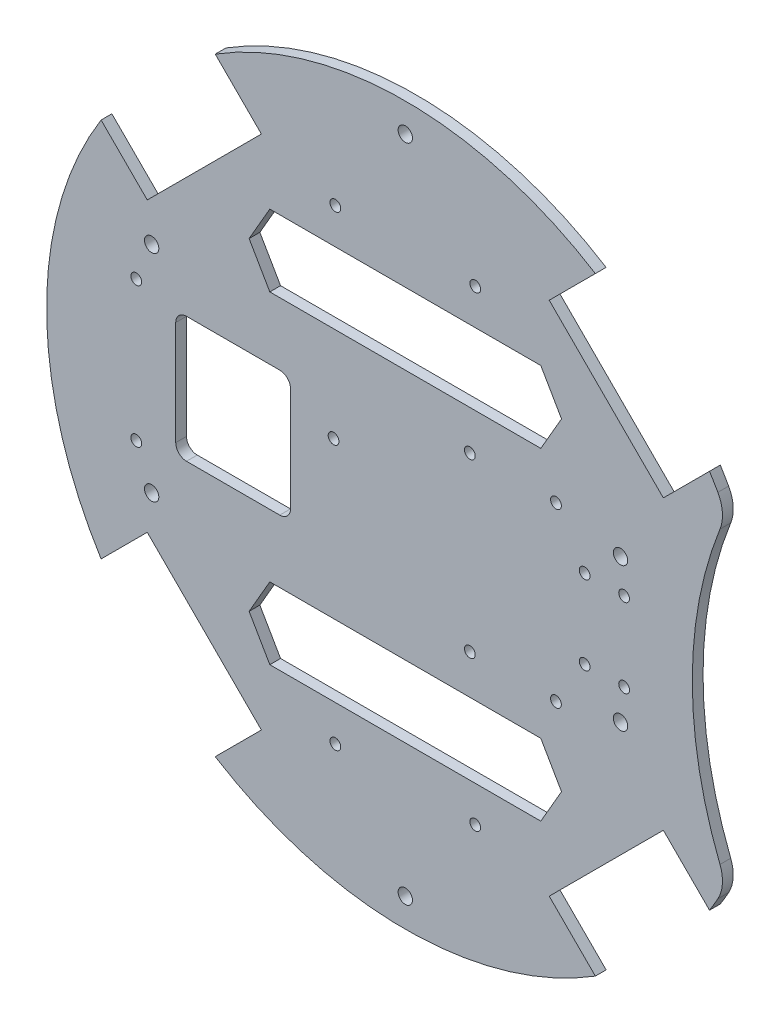
SolidWorks part; units mm, degrees
ref_plane "Alzado" through (0, 0, 0) normal (0, 0, 1) x (1, 0, 0)
ref_plane "Planta" through (0, 0, 0) normal (0, 1, 0) x (1, 0, 0)
ref_plane "Vista lateral" through (0, 0, 0) normal (1, 0, 0) x (0, 0, -1)
sketch "Croquis1" plane through (0, 0, 0) normal (0, 0, 1) x (1, 0, 0)
  circle A0 centre (0, 0) radius 100
  dimension "D1" = 200
extrude "Saliente-Extruir1" add sketch "Croquis1" along normal blind 3
sketch "Croquis3" plane through (0, 0, 3) normal (0, 0, 1) x (1, 0, 0)
  line L0 (0, 0) -> (190, 0) construction
  circle A0 centre (190, 0) radius 110
  dimension "D1" = 220
  dimension "D2" = 190
extrude "Cortar-Extruir1" cut sketch "Croquis3" against normal blind 3
fillet "Redondeo1" radius 10 2 edges at (89.4737, -44.6594, 1.5) (89.4737, 44.6594, 1.5)
sketch "Croquis7" plane through (0, 0, 3) normal (0, 0, 1) x (1, 0, 0)
  line L0 (-71.9393, -40.1195) -> (-40.1195, -71.9393)
  line L1 (-71.9393, -40.1195) -> (-89.617, -57.7972)
  line L2 (-40.1195, -71.9393) -> (-57.7972, -89.617)
  line L3 (-89.617, -57.7972) -> (-57.7972, -89.617)
  line L6 (0, -100) -> (0, 100) construction
  line L7 (-100, 0) -> (80, 0) construction
  line L8 (-40.1195, 71.9393) -> (-71.9393, 40.1195)
  line L9 (-40.1195, 71.9393) -> (-57.7972, 89.617)
  line L10 (-57.7972, 89.617) -> (-89.617, 57.7972)
  line L11 (-71.9393, 40.1195) -> (-89.617, 57.7972)
  line L12 (71.9393, 40.1195) -> (40.1195, 71.9393)
  line L13 (71.9393, 40.1195) -> (89.617, 57.7972)
  line L14 (89.617, 57.7972) -> (57.7972, 89.617)
  line L15 (40.1195, 71.9393) -> (57.7972, 89.617)
  line L16 (40.1195, -71.9393) -> (71.9393, -40.1195)
  line L17 (40.1195, -71.9393) -> (57.7972, -89.617)
  line L18 (57.7972, -89.617) -> (89.617, -57.7972)
  line L19 (71.9393, -40.1195) -> (89.617, -57.7972)
  line L20 (70.7107, -70.7107) -> (-70.7107, 70.7107) construction
  line L21 (-70.7107, -70.7107) -> (70.7107, 70.7107) construction
  arc A0 (87.1345, 49.0671) -> (87.1345, -49.0671) centre (0, 0) ccw construction
  arc A1 (87.1345, 49.0671) -> (87.1345, -49.0671) centre (0, 0) ccw construction
  arc A4 (87.7193, 40.4803) -> (87.7193, -40.4803) centre (190, 0) ccw construction
  point P24 (0, 0)
  dimension "D1" = 22.5
  dimension "D2" = 45
  dimension "D3" = 25
  dimension "D4" = 45
  dimension "D5" = 200
  dimension "D6" = 4
  dimension "D7" = 79.2376
  dimension "D8" = 22.5
  dimension "D9" = 200
  dimension "D10" = 45
  dimension "D11" = 90
  dimension "D12" = 79.2376
extrude "Cortar-Extruir3" cut sketch "Croquis7" against normal blind 10
sketch "Croquis10" plane through (0, 0, 3) normal (0, 0, 1) x (1, 0, 0)
  line L0 (80, 0) -> (-100, 0) construction
  circle A0 centre (-20, 8.5) radius 1.5
  arc A1 (-84.8075, 52.9877) -> (-84.8075, -52.9877) centre (0, 0) ccw construction
  arc A5 (87.7193, 40.4803) -> (87.7193, -40.4803) centre (190, 0) ccw construction
  point P5 (0, 0)
  dimension "D1" = 3
  dimension "D2" = 8.5
  dimension "D3" = 20
extrude "Cortar-Extruir4" cut sketch "Croquis10" against normal through all
sketch "Croquis12" plane through (0, 0, 0) normal (0, 0, -1) x (-1, 0, 0)
  line L0 (-80, 0) -> (100, 0) construction
  line L1 (-61, 0) -> (-61, -11) construction
  line L2 (-61, 0) -> (-61, 11) construction
  line L5 (-50, 11) -> (-50, -11) construction
  line L6 (0, 100) -> (0, -100) construction
  circle A4 centre (-61, 11) radius 1.5
  circle A6 centre (-61, -11) radius 1.5
  circle A7 centre (-50, 11) radius 1.5
  circle A8 centre (-50, -11) radius 1.5
  arc A9 (52.9877, 84.8075) -> (-52.9877, 84.8075) centre (0, 0) ccw construction
  arc A10 (-52.9877, -84.8075) -> (52.9877, -84.8075) centre (0, 0) ccw construction
  arc A11 (-87.7193, -40.4803) -> (-87.7193, 40.4803) centre (-190, 0) ccw construction
  arc A12 (84.8075, -52.9877) -> (84.8075, 52.9877) centre (0, 0) ccw construction
  dimension "D4" = 11
  dimension "D5" = 3
  dimension "D6" = 3
  dimension "D7" = 11
  dimension "D1" = 3
  dimension "D2" = 3
  dimension "D3" = 50
  dimension "D8" = 11
  dimension "D9" = 22
  dimension "D10" = 11
extrude "Cortar-Extruir6" cut sketch "Croquis12" against normal through all
sketch "Croquis13" plane through (0, 0, 0) normal (0, 0, -1) x (-1, 0, 0)
  line L0 (0, 100) -> (0, -100) construction
  line L1 (100, 0) -> (-100, 0) construction
  line L2 (-70.7107, -70.7107) -> (70.7107, 70.7107) construction
  line L3 (-70.7093, 70.7093) -> (70.712, -70.712) construction
  line L4 (-70.7093, 70.7093) -> (-70.7107, -70.7107) construction
  line L5 (-70.7107, -70.7107) -> (70.712, -70.712) construction
  line L6 (70.712, -70.712) -> (70.7107, 70.7107) construction
  line L7 (70.7107, 70.7107) -> (-70.7093, 70.7093) construction
  arc A0 (52.9877, 84.8075) -> (-52.9877, 84.8075) centre (0, 0) ccw construction
  arc A1 (-52.9877, -84.8075) -> (52.9877, -84.8075) centre (0, 0) ccw construction
  arc A2 (84.8075, -52.9877) -> (84.8075, 52.9877) centre (0, 0) ccw construction
  circle A3 centre (0, 92) radius 2
  circle A4 centre (0, -92) radius 2
  circle A7 centre (70.7111, 30) radius 2
  circle A8 centre (70.7116, -30) radius 2
  circle A11 centre (-60, 20) radius 2
  circle A12 centre (-60, -20) radius 2
  dimension "D10" = 4
  dimension "D11" = 92
  dimension "D12" = 4
  dimension "D13" = 92
  dimension "D14" = 4
  dimension "D15" = 4
  dimension "D16" = 30
  dimension "D17" = 30
  dimension "D18" = 4
  dimension "D19" = 4
  dimension "D20" = 20
  dimension "D21" = 20
  dimension "D22" = 60
  dimension "D23" = 60
  dimension "D1" = 200
  dimension "D2" = 0
  dimension "D3" = 0
  dimension "D4" = 200
  dimension "D5" = 200
  dimension "D6" = 45
  dimension "D7" = 45
  dimension "D8" = 141.42
  dimension "D9" = 141.42
extrude "Cortar-Extruir7" cut sketch "Croquis13" against normal through all
sketch "Croquis15" plane through (0, 0, 0) normal (0, 0, -1) x (-1, 0, 0)
  line L0 (0, -100) -> (0, 100) construction
  line L1 (-32, 55) -> (32, 55)
  line L2 (-32, 55) -> (-32, 35)
  line L3 (-32, 35) -> (32, 35)
  line L4 (32, 55) -> (32, 35)
  line L5 (100, 0) -> (-80, 0) construction
  line L6 (37.7735, -35) -> (43.547, -45)
  line L7 (-43.547, 45) -> (-37.7735, 35)
  line L8 (-37.7735, 35) -> (-26.2265, 35)
  line L9 (-26.2265, 35) -> (-20.453, 45)
  line L10 (-20.453, 45) -> (-26.2265, 55)
  line L11 (-26.2265, 55) -> (-37.7735, 55)
  line L12 (-37.7735, 55) -> (-43.547, 45)
  line L13 (43.547, 45) -> (37.7735, 55)
  line L14 (37.7735, 55) -> (26.2265, 55)
  line L15 (26.2265, 55) -> (20.453, 45)
  line L16 (20.453, 45) -> (26.2265, 35)
  line L17 (26.2265, 35) -> (37.7735, 35)
  line L18 (37.7735, 35) -> (43.547, 45)
  line L19 (26.2265, -35) -> (37.7735, -35)
  line L20 (20.453, -45) -> (26.2265, -35)
  line L21 (26.2265, -55) -> (20.453, -45)
  line L22 (37.7735, -55) -> (26.2265, -55)
  line L23 (43.547, -45) -> (37.7735, -55)
  line L24 (-37.7735, -55) -> (-43.547, -45)
  line L25 (-26.2265, -55) -> (-37.7735, -55)
  line L26 (-20.453, -45) -> (-26.2265, -55)
  line L27 (-26.2265, -35) -> (-20.453, -45)
  line L28 (-37.7735, -35) -> (-26.2265, -35)
  line L29 (-43.547, -45) -> (-37.7735, -35)
  line L30 (-32, -35) -> (32, -35)
  line L31 (32, -55) -> (32, -35)
  line L32 (-32, -55) -> (32, -55)
  line L33 (-32, -55) -> (-32, -35)
  line L35 (32, 17.5) -> (64, 17.5)
  line L36 (32, 17.5) -> (32, -17.5)
  line L37 (32, -17.5) -> (64, -17.5)
  line L38 (64, 17.5) -> (64, -17.5)
  arc A0 (-52.9877, -84.8075) -> (52.9877, -84.8075) centre (0, 0) ccw construction
  arc A1 (52.9877, 84.8075) -> (-52.9877, 84.8075) centre (0, 0) ccw construction
  arc A2 (84.8075, -52.9877) -> (84.8075, 52.9877) centre (0, 0) ccw construction
  arc A3 (-87.7193, -40.4803) -> (-87.7193, 40.4803) centre (-190, 0) ccw construction
  circle A4 centre (-32, 45) radius 10 construction
  circle A5 centre (32, 45) radius 10 construction
  dimension "D1" = 35
  dimension "D2" = 64
  dimension "D3" = 20
  dimension "D4" = 32
  dimension "D5" = 0
  dimension "D6" = 0
  dimension "D7" = 35
  dimension "D8" = 32
  dimension "D9" = 17.5
  dimension "D10" = 32
extrude "Cortar-Extruir8" cut sketch "Croquis15" against normal through all contours L16 L15 L1 L10 L9 L3 | L9 L10 L1 L2 L3 | L11 L12 L7 L8 L2 | L17 L18 L13 L14 L4 | L15 L16 L3 L4 L1 | L26 L32 L21 L20 L30 L27 | L22 L31 L19 L20 L21 | L31 L22 L23 L6 L19 | L33 L25 L26 L27 L28 | L25 L33 L28 L29 L24 | L38 L35 L36 L37 | L36 L35 L38 L37 region at (27.5095, 45, 0) region at (36.4905, 45, 0) region at (0, 45, 0) region at (-27.5095, 45, 0) region at (-36.4905, 45, 0) region at (-36.4905, -45, 0) region at (-27.5095, -45, 0) region at (0, -45, 0) region at (27.5095, -45, 0) region at (36.4905, -45, 0) region at (-48, 0, 0)
fillet "Redondeo2" radius 3 4 edges at (-64, -17.5, 1.5) (-32, -17.5, 1.5) (-64, 17.5, 1.5) (-32, 17.5, 1.5)
sketch "Croquis16" plane through (0, 0, 0) normal (0, 0, -1) x (-1, 0, 0)
  line L0 (0, 100) -> (0, -100) construction
  line L1 (100, 0) -> (-80, 0) construction
  arc A0 (52.9877, 84.8075) -> (-52.9877, 84.8075) centre (0, 0) ccw construction
  arc A1 (-52.9877, -84.8075) -> (52.9877, -84.8075) centre (0, 0) ccw construction
  arc A2 (84.8075, -52.9877) -> (84.8075, 52.9877) centre (0, 0) ccw construction
  arc A3 (-87.7193, -40.4803) -> (-87.7193, 40.4803) centre (-190, 0) ccw construction
  circle A4 centre (-19.5, 65) radius 1.5
  circle A5 centre (19.5, 65) radius 1.5
  circle A6 centre (19.5, -65) radius 1.5
  circle A7 centre (-19.5, -65) radius 1.5
  circle A8 centre (-42, 24) radius 1.5
  circle A9 centre (-42, -24) radius 1.5
  circle A10 centre (-18, -24) radius 1.5
  circle A11 centre (-18, 24) radius 1.5
  circle A14 centre (75, 19.5) radius 1.5
  circle A15 centre (75, -19.5) radius 1.5
  dimension "D1" = 3
  dimension "D2" = 3
  dimension "D3" = 39
  dimension "D4" = 19.5
  dimension "D5" = 65
  dimension "D6" = 65
  dimension "D7" = 24
  dimension "D8" = 24
  dimension "D9" = 24
  dimension "D10" = 18
  dimension "D11" = 18
  dimension "D12" = 24
  dimension "D13" = 24
  dimension "D14" = 24
  dimension "D15" = 3
  dimension "D16" = 3
  dimension "D17" = 3
  dimension "D18" = 3
  dimension "D25" = 3
  dimension "D26" = 3
  dimension "D27" = 19.5
  dimension "D28" = 19.5
  dimension "D29" = 75
  dimension "D30" = 75
extrude "Cortar-Extruir9" cut sketch "Croquis16" against normal through all
